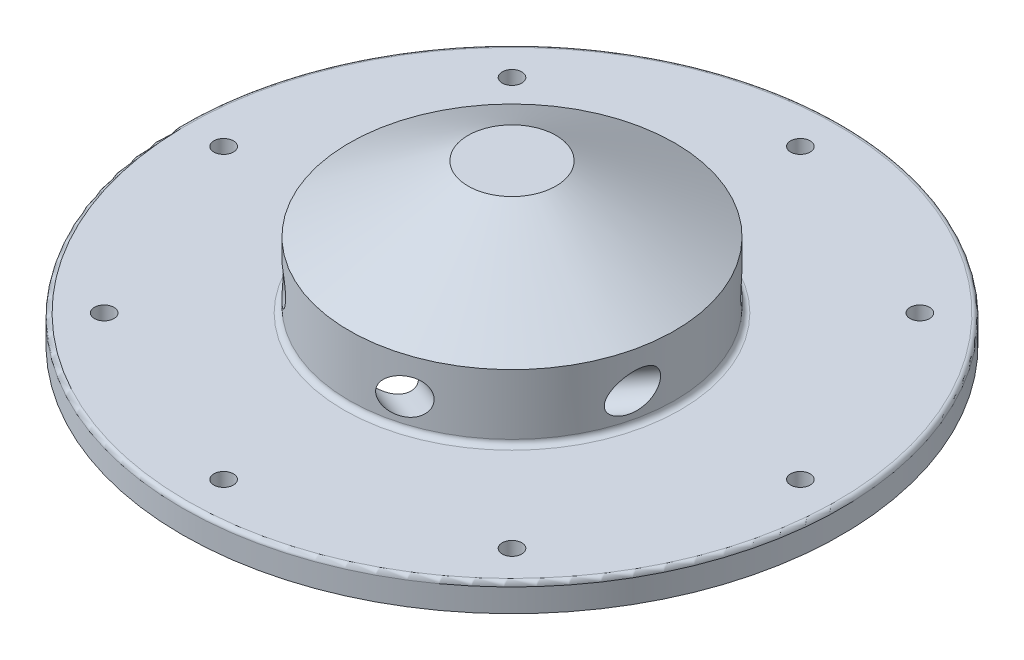
SolidWorks part; units mm, degrees
material "7075-T6 (SN)"
ref_plane "Front Plane" through (0, 0, 0) normal (0, 0, 1) x (1, 0, 0)
ref_plane "Top Plane" through (0, 0, 0) normal (0, 1, 0) x (1, 0, 0)
ref_plane "Right Plane" through (0, 0, 0) normal (1, 0, 0) x (0, 0, -1)
sketch "Sketch2" plane through (0, 0, 0) normal (0, 1, 0) x (1, 0, 0)
  circle A0 centre (0, 0) radius 38.1
  dimension "D1" = 76.2
extrude "Boss-Extrude1" add sketch "Sketch2" along normal blind 3.175
hole_wizard "Tap Drill for #4-40 Tap1" positions "Sketch3" profile "Sketch4" hole size "#4-40" standard "ANSI Inch" end condition through all
sketch "Sketch3" plane through (0, 0, 0) normal (0, -1, 0) x (-1, 0, 0)
  point P0 (0, -33.3375)
  dimension "D1" = 33.3375
sketch "Sketch4" plane through (0, 0, 33.3375) normal (1, 0, 0) x (0, 0, -1)
  line L0 (0, 0) -> (0, 3.175)
  line L1 (0, 3.175) -> (1.1303, 3.175)
  line L2 (1.1303, 3.175) -> (1.1303, 0)
  line L5 (1.1303, 0) -> (0, 0)
  line L11 (0, -6.35) -> (0, 107.95) construction
  dimension "Thru Hole Dia." = 2.2606
  dimension "Thru Hole Depth" = 3.175
pattern_circular "CirPattern1" count 8 over 360 about axis through (0, 0, 0) along (0, 1, 0) of "Tap Drill for #4-40 Tap1"
sketch "Sketch5" plane through (0, 3.175, 0) normal (0, 1, 0) x (1, 0, 0)
  circle A0 centre (0, 0) radius 28.575
  dimension "D1" = 57.15
sketch "Sketch7" plane through (0, 3.175, 0) normal (0, 1, 0) x (1, 0, 0)
  circle A0 centre (0, 0) radius 18.81
  dimension "D1" = 37.62
extrude "Boss-Extrude2" add sketch "Sketch7" along normal blind 7.62
sketch "Sketch8" plane through (0, 0, 0) normal (0, -1, 0) x (1, 0, 0)
  circle A0 centre (0, 0) radius 15
  dimension "D1" = 30
extrude "Cut-Extrude1" cut sketch "Sketch8" against normal blind 8.89
sketch "Sketch13" plane through (0, 10.795, 0) normal (0, 1, 0) x (1, 0, 0)
  circle A0 centre (0, 0) radius 18.81
  circle A1 centre (0, 0) radius 18.81 construction
  dimension "D1" = 0
ref_plane "Plane2" through (0, 18.415, 0) normal (0, 1, 0) x (1, 0, 0)
sketch "Sketch14" plane through (0, 18.415, 0) normal (0, 1, 0) x (1, 0, 0)
  circle A0 centre (0, 0) radius 5.08
  dimension "D1" = 10.16
loft "Loft2" add profiles "Sketch14", "Sketch13" connector at (-0.0647, 18.415, 5.0796) connector at (0, 10.795, 18.81)
fillet "Fillet1" radius 0.635 1 edges at (0, 8.89, -15)
fillet "Fillet3" radius 0.5 1 edges at (0, 3.175, 38.1)
ref_plane "Plane4" through (0, 7.62, 0) normal (0, 1, 0) x (1, 0, 0)
fillet "Fillet2" radius 0.635 1 edges at (0, 3.175, 18.81)
ref_axis "Axis1" through (41.91, 7.62, 0) along (-1, 0, 0)
ref_plane "Plane3" through (0, 0.5104, 1.905) normal (0, 0.2588, 0.9659) x (-1, 0, 0)
sketch "Sketch16" plane through (0, 0.5104, 1.905) normal (0, 0.2588, 0.9659) x (-1, 0, 0)
  circle A0 centre (12.71, -2.7899) radius 1.98
  dimension "D1" = 3.96
  dimension "D2" = 12.71
  dimension "D3" = 2.7899
extrude "Cut-Extrude2" cut sketch "Sketch16" along normal through all
pattern_circular "CirPattern2" count 6 over 360 about axis through (0, 10.795, 0) along (0, 1, 0) of "Cut-Extrude2"
